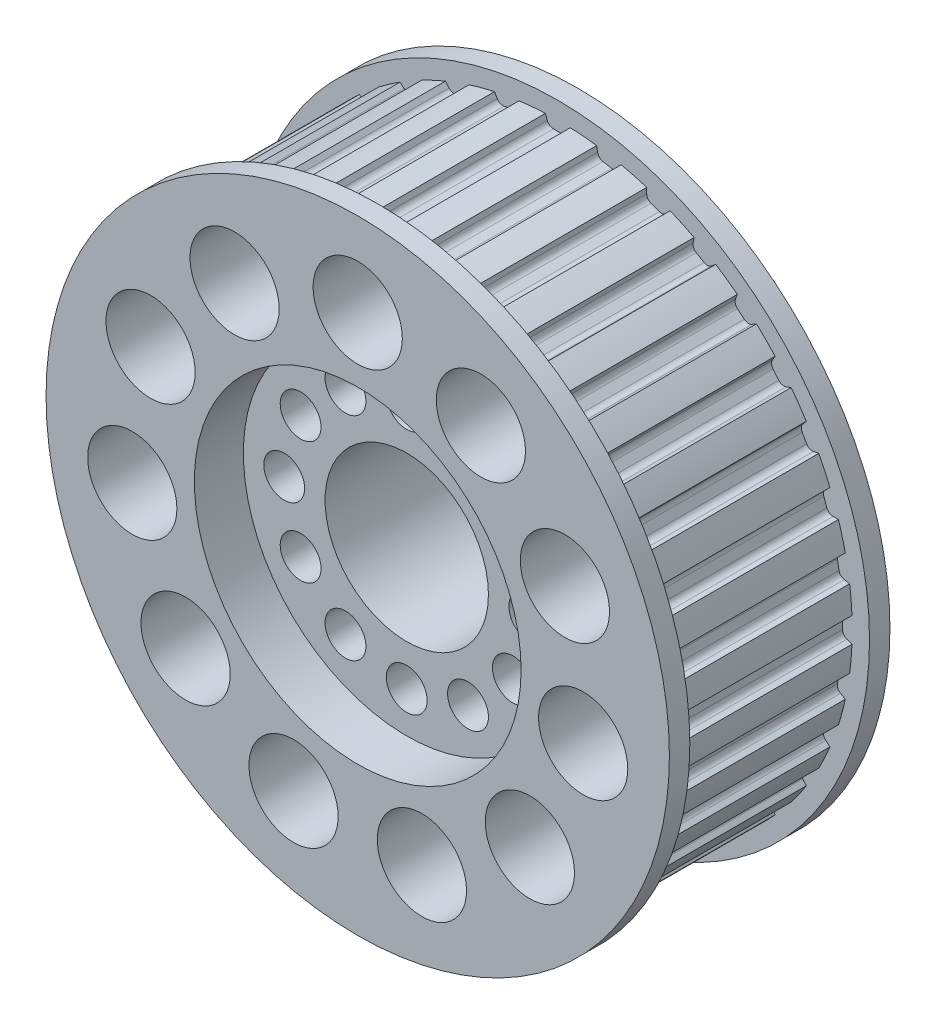
SolidWorks part; units mm, degrees
note: '?' marks a value the reader was unsure of.
extrude "Base-Extrude" add sketch "Sketch1" along normal mid plane 50
sketch "Sketch1" plane through (0, 0, 0) normal (0, 0, 1) x (1, 0, 0)
  circle A0 centre (0, 0) radius 72.0656
  dimension "D1" = 144.1313
material "Nylon 6/10"
ref_plane "Front" through (0, 0, 0) normal (0, 0, 1) x (1, 0, 0)
ref_plane "Top" through (0, 0, 0) normal (0, 1, 0) x (1, 0, 0)
ref_plane "Right" through (0, 0, 0) normal (1, 0, 0) x (0, 0, -1)
sketch "Sketch2" plane through (0, 0, 0) normal (0, 0, 1) x (1, 0, 0)
  line L0 (0, 0) -> (0, 56.1155) construction
  line L1 (-3.05, 72.0011) -> (-2.2129, 69.7011)
  line L2 (-2.2129, 69.7011) -> (2.2129, 69.7011)
  line L3 (2.2129, 69.7011) -> (3.05, 72.0011)
  circle A0 centre (0, 0) radius 72.0656 construction
  dimension "D1" = 6.1
  dimension "D2" = 3.05
  dimension "D3" = 2.3
  dimension "D4" = 40
  dimension "D5" = 20
extrude "Cut-Extrude1" cut sketch "Sketch2" against normal through all and the other way through all
fillet "Fillet1" radius 1.6 2 edges at (-2.2129, 69.7011, 0) (2.2129, 69.7011, 0)
ref_axis "PulleyAxis" through (0, 0, -29.7) along (0, 0, 1)?
pattern_circular "CirPattern1" count 36 every 10 about axis through (0, 0, 0) along (0, 0, 1) of "Fillet1", "Cut-Extrude1"
ref_plane "Plane1" through (228.6, 0, 0) normal (1, 0, 0) x (0, 0, -1)
ref_axis "AxisDistance" through (228.6, 0, 29.7) along (0, 0, -1)?
sketch "Sketch7" plane through (0, 0, 25) normal (0, 0, 1) x (1, 0, 0)
  circle A0 centre (0, 0) radius 40
  dimension "D1" = 80
extrude "Cut-Extrude4" cut sketch "Sketch7" against normal blind 10
sketch "Sketch12" plane through (0, 0, 25) normal (0, 0, 1) x (1, 0, 0)
  circle A0 centre (0, 0) radius 40
  circle A1 centre (0, 0) radius 75
  dimension "D2" = 150
  dimension "D1" = 80
extrude "Cut-Extrude7" cut sketch "Sketch12" against normal blind 3
sketch "Sketch13" plane through (0, 0, -25) normal (0, 0, -1) x (-1, 0, 0)
  circle A0 centre (0, 0) radius 40
  circle A1 centre (0, 0) radius 75
  dimension "D2" = 150
  dimension "D1" = 80
extrude "Cut-Extrude8" cut sketch "Sketch13" against normal blind 3
sketch "Sketch15" plane through (0, 0, 22) normal (0, 0, 1) x (1, 0, 0)
  line L0 (0, 69.7011) -> (0, 0) construction
  line L1 (-1.0925, 69.7011) -> (1.0925, 69.7011) construction
  circle A0 centre (0, 60) radius 1.5
  dimension "D1" = 3
  dimension "D2" = 60
extrude "Cut-Extrude10" cut sketch "Sketch15" against normal blind 60
pattern_circular "CirPattern2" count 12 over 360 about axis through (0, 0, 0) along (0, 0, 1) of "Cut-Extrude10"
sketch "Sketch16" plane through (0, 0, -25) normal (0, 0, -1) x (-1, 0, 0)
  line L0 (0, 0) -> (0, 40) construction
  circle A0 centre (0, 0) radius 40 construction
  circle A1 centre (0, 30) radius 5
  circle A2 centre (15, 25.9808) radius 5
  circle A3 centre (25.9808, 15) radius 5
  circle A4 centre (30, 0) radius 5
  circle A5 centre (25.9808, -15) radius 5
  circle A6 centre (15, -25.9808) radius 5
  circle A7 centre (0, -30) radius 5
  circle A8 centre (-15, -25.9808) radius 5
  circle A9 centre (-25.9808, -15) radius 5
  circle A10 centre (-30, 0) radius 5
  circle A11 centre (-25.9808, 15) radius 5
  circle A12 centre (-15, 25.9808) radius 5
  dimension "D1" = 10
  dimension "D2" = 30
extrude "Cut-Extrude11" cut sketch "Sketch16" against normal blind 50
sketch "Sketch17" plane through (0, 0, -25) normal (0, 0, -1) x (-1, 0, 0)
  circle A0 centre (0, 0) radius 13.5
  dimension "D1" = 27
extrude "Cut-Extrude12" cut sketch "Sketch17" against normal blind 50
sketch "Sketch19" plane through (0, 0, 22) normal (0, 0, 1) x (1, 0, 0)
  line L0 (0, 60) -> (30, 51.9615) construction
  line L1 (0, 0) -> (15, 55.9808) construction
  circle A0 centre (14.235, 53.1259) radius 10
  dimension "D1" = 55
  dimension "D2" = 20
extrude "Cut-Extrude14" cut sketch "Sketch19" against normal blind 60
pattern_circular "CirPattern3" count 12 over 360 about axis through (0, 0, 0) along (0, 0, 1) of "Cut-Extrude14"
sketch "Sketch20" plane through (0, 0, -25) normal (0, 0, -1) x (-1, 0, 0)
  circle A0 centre (0, 0) radius 40
  dimension "D1" = 80
extrude "Cut-Extrude15" cut sketch "Sketch20" against normal blind 8
sketch "Sketch24" plane through (0, 0, -17) normal (0, 0, -1) x (-1, 0, 0)
  circle A0 centre (0, 0) radius 16
  dimension "D1" = 32
extrude "Cut-Extrude18" cut sketch "Sketch24" against normal blind 10
sketch "Sketch25" plane through (0, 0, 15) normal (0, 0, 1) x (1, 0, 0)
  circle A0 centre (0, 0) radius 16
  dimension "D1" = 32
extrude "Cut-Extrude19" cut sketch "Sketch25" against normal blind 10
sketch "Sketch26" plane through (0, 0, 22) normal (0, 0, 1) x (1, 0, 0)
  line L108 (-13.1794, -68.4524) -> (-11.0275, -68.8319)
  line L109 (-9.7297, -70.1297) -> (-9.4992, -71.4368)
  line L110 (-3.05, -72.0011) -> (-2.596, -70.7538)
  line L111 (-1.0925, -69.7011) -> (1.0925, -69.7011)
  line L112 (2.596, -70.7538) -> (3.05, -72.0011)
  line L113 (9.4992, -71.4368) -> (9.7297, -70.1297)
  line L114 (11.0275, -68.8319) -> (13.1794, -68.4524)
  line L115 (14.8429, -69.2281) -> (15.5065, -70.3776)
  line L116 (21.7598, -68.702) -> (21.7598, -67.3748)
  line L117 (22.8125, -65.8712) -> (24.8658, -65.1239)
  line L118 (26.6387, -65.599) -> (27.4919, -66.6157)
  line L119 (33.3592, -63.8798) -> (33.1287, -62.5726)
  line L120 (33.9044, -60.9092) -> (35.7967, -59.8166)
  line L121 (37.6252, -59.9766) -> (38.6419, -60.8298)
  line L122 (43.945, -57.1165) -> (43.491, -55.8693)
  line L123 (43.9661, -54.0964) -> (45.6399, -52.6918)
  line L124 (47.4684, -52.5319) -> (48.6178, -53.1955)
  line L125 (53.1955, -48.6178) -> (52.5319, -47.4684)
  line L126 (52.6918, -45.6399) -> (54.0964, -43.9661)
  line L127 (55.8693, -43.491) -> (57.1165, -43.945)
  line L128 (60.8298, -38.6419) -> (59.9766, -37.6252)
  line L129 (59.8166, -35.7967) -> (60.9092, -33.9044)
  line L130 (62.5726, -33.1287) -> (63.8798, -33.3592)
  line L131 (66.6157, -27.4919) -> (65.599, -26.6387)
  line L132 (65.1239, -24.8658) -> (65.8712, -22.8125)
  line L133 (67.3748, -21.7598) -> (68.702, -21.7598)
  line L134 (70.3776, -15.5065) -> (69.2281, -14.8429)
  line L135 (68.4524, -13.1794) -> (68.8319, -11.0275)
  line L136 (70.1297, -9.7297) -> (71.4368, -9.4992)
  line L137 (72.0011, -3.05) -> (70.7538, -2.596)
  line L138 (69.7011, -1.0925) -> (69.7011, 1.0925)
  line L139 (70.7538, 2.596) -> (72.0011, 3.05)
  line L140 (71.4368, 9.4992) -> (70.1297, 9.7297)
  line L141 (68.8319, 11.0275) -> (68.4524, 13.1794)
  line L142 (69.2281, 14.8429) -> (70.3776, 15.5065)
  line L143 (68.702, 21.7598) -> (67.3748, 21.7598)
  line L144 (65.8712, 22.8125) -> (65.1239, 24.8658)
  line L145 (65.599, 26.6387) -> (66.6157, 27.4919)
  line L146 (63.8798, 33.3592) -> (62.5726, 33.1287)
  line L147 (60.9092, 33.9044) -> (59.8166, 35.7967)
  line L148 (59.9766, 37.6252) -> (60.8298, 38.6419)
  line L149 (57.1165, 43.945) -> (55.8693, 43.491)
  line L150 (54.0964, 43.9661) -> (52.6918, 45.6399)
  line L151 (52.5319, 47.4684) -> (53.1955, 48.6178)
  line L152 (48.6178, 53.1955) -> (47.4684, 52.5319)
  line L153 (45.6399, 52.6918) -> (43.9661, 54.0964)
  line L154 (43.491, 55.8693) -> (43.945, 57.1165)
  line L155 (38.6419, 60.8298) -> (37.6252, 59.9766)
  line L156 (35.7967, 59.8166) -> (33.9044, 60.9092)
  line L157 (33.1287, 62.5726) -> (33.3592, 63.8798)
  line L158 (27.4919, 66.6157) -> (26.6387, 65.599)
  line L159 (24.8658, 65.1239) -> (22.8125, 65.8712)
  line L160 (21.7598, 67.3748) -> (21.7598, 68.702)
  line L161 (15.5065, 70.3776) -> (14.8429, 69.2281)
  line L162 (13.1794, 68.4524) -> (11.0275, 68.8319)
  line L163 (9.7297, 70.1297) -> (9.4992, 71.4368)
  line L164 (3.05, 72.0011) -> (2.596, 70.7538)
  line L165 (1.0925, 69.7011) -> (-1.0925, 69.7011)
  line L166 (-2.596, 70.7538) -> (-3.05, 72.0011)
  line L167 (-9.4992, 71.4368) -> (-9.7297, 70.1297)
  line L168 (-11.0275, 68.8319) -> (-13.1794, 68.4524)
  line L169 (-14.8429, 69.2281) -> (-15.5065, 70.3776)
  line L170 (-21.7598, 68.702) -> (-21.7598, 67.3748)
  line L171 (-22.8125, 65.8712) -> (-24.8658, 65.1239)
  line L172 (-26.6387, 65.599) -> (-27.4919, 66.6157)
  line L173 (-33.3592, 63.8798) -> (-33.1287, 62.5726)
  line L174 (-33.9044, 60.9092) -> (-35.7967, 59.8166)
  line L175 (-37.6252, 59.9766) -> (-38.6419, 60.8298)
  line L176 (-43.945, 57.1165) -> (-43.491, 55.8693)
  line L177 (-43.9661, 54.0964) -> (-45.6399, 52.6918)
  line L178 (-47.4684, 52.5319) -> (-48.6178, 53.1955)
  line L179 (-53.1955, 48.6178) -> (-52.5319, 47.4684)
  line L180 (-52.6918, 45.6399) -> (-54.0964, 43.9661)
  line L181 (-55.8693, 43.491) -> (-57.1165, 43.945)
  line L182 (-60.8298, 38.6419) -> (-59.9766, 37.6252)
  line L183 (-59.8166, 35.7967) -> (-60.9092, 33.9044)
  line L184 (-62.5726, 33.1287) -> (-63.8798, 33.3592)
  line L185 (-66.6157, 27.4919) -> (-65.599, 26.6387)
  line L186 (-65.1239, 24.8658) -> (-65.8712, 22.8125)
  line L187 (-67.3748, 21.7598) -> (-68.702, 21.7598)
  line L188 (-70.3776, 15.5065) -> (-69.2281, 14.8429)
  line L189 (-68.4524, 13.1794) -> (-68.8319, 11.0275)
  line L190 (-70.1297, 9.7297) -> (-71.4368, 9.4992)
  line L191 (-72.0011, 3.05) -> (-70.7538, 2.596)
  line L192 (-69.7011, 1.0925) -> (-69.7011, -1.0925)
  line L193 (-70.7538, -2.596) -> (-72.0011, -3.05)
  line L194 (-71.4368, -9.4992) -> (-70.1297, -9.7297)
  line L195 (-68.8319, -11.0275) -> (-68.4524, -13.1794)
  line L196 (-69.2281, -14.8429) -> (-70.3776, -15.5065)
  line L197 (-68.702, -21.7598) -> (-67.3748, -21.7598)
  line L198 (-65.8712, -22.8125) -> (-65.1239, -24.8658)
  line L199 (-65.599, -26.6387) -> (-66.6157, -27.4919)
  line L200 (-63.8798, -33.3592) -> (-62.5726, -33.1287)
  line L201 (-60.9092, -33.9044) -> (-59.8166, -35.7967)
  line L202 (-59.9766, -37.6252) -> (-60.8298, -38.6419)
  line L203 (-57.1165, -43.945) -> (-55.8693, -43.491)
  line L204 (-54.0964, -43.9661) -> (-52.6918, -45.6399)
  line L205 (-52.5319, -47.4684) -> (-53.1955, -48.6178)
  line L206 (-48.6178, -53.1955) -> (-47.4684, -52.5319)
  line L207 (-45.6399, -52.6918) -> (-43.9661, -54.0964)
  line L208 (-43.491, -55.8693) -> (-43.945, -57.1165)
  line L209 (-38.6419, -60.8298) -> (-37.6252, -59.9766)
  line L210 (-35.7967, -59.8166) -> (-33.9044, -60.9092)
  line L211 (-33.1287, -62.5726) -> (-33.3592, -63.8798)
  line L212 (-27.4919, -66.6157) -> (-26.6387, -65.599)
  line L213 (-24.8658, -65.1239) -> (-22.8125, -65.8712)
  line L214 (-21.7598, -67.3748) -> (-21.7598, -68.702)
  line L215 (-15.5065, -70.3776) -> (-14.8429, -69.2281)
  line L216 (-13.1794, -68.4524) -> (-11.0275, -68.8319)
  line L217 (-9.7297, -70.1297) -> (-9.4992, -71.4368)
  line L218 (-3.05, -72.0011) -> (-2.596, -70.7538)
  line L219 (-1.0925, -69.7011) -> (1.0925, -69.7011)
  line L220 (2.596, -70.7538) -> (3.05, -72.0011)
  line L221 (9.4992, -71.4368) -> (9.7297, -70.1297)
  line L222 (11.0275, -68.8319) -> (13.1794, -68.4524)
  line L223 (14.8429, -69.2281) -> (15.5065, -70.3776)
  line L224 (21.7598, -68.702) -> (21.7598, -67.3748)
  line L225 (22.8125, -65.8712) -> (24.8658, -65.1239)
  line L226 (26.6387, -65.599) -> (27.4919, -66.6157)
  line L227 (33.3592, -63.8798) -> (33.1287, -62.5726)
  line L228 (33.9044, -60.9092) -> (35.7967, -59.8166)
  line L229 (37.6252, -59.9766) -> (38.6419, -60.8298)
  line L230 (43.945, -57.1165) -> (43.491, -55.8693)
  line L231 (43.9661, -54.0964) -> (45.6399, -52.6918)
  line L232 (47.4684, -52.5319) -> (48.6178, -53.1955)
  line L233 (53.1955, -48.6178) -> (52.5319, -47.4684)
  line L234 (52.6918, -45.6399) -> (54.0964, -43.9661)
  line L235 (55.8693, -43.491) -> (57.1165, -43.945)
  line L236 (60.8298, -38.6419) -> (59.9766, -37.6252)
  line L237 (59.8166, -35.7967) -> (60.9092, -33.9044)
  line L238 (62.5726, -33.1287) -> (63.8798, -33.3592)
  line L239 (66.6157, -27.4919) -> (65.599, -26.6387)
  line L240 (65.1239, -24.8658) -> (65.8712, -22.8125)
  line L241 (67.3748, -21.7598) -> (68.702, -21.7598)
  line L242 (70.3776, -15.5065) -> (69.2281, -14.8429)
  line L243 (68.4524, -13.1794) -> (68.8319, -11.0275)
  line L244 (70.1297, -9.7297) -> (71.4368, -9.4992)
  line L245 (72.0011, -3.05) -> (70.7538, -2.596)
  line L246 (69.7011, -1.0925) -> (69.7011, 1.0925)
  line L247 (70.7538, 2.596) -> (72.0011, 3.05)
  line L248 (71.4368, 9.4992) -> (70.1297, 9.7297)
  line L249 (68.8319, 11.0275) -> (68.4524, 13.1794)
  line L250 (69.2281, 14.8429) -> (70.3776, 15.5065)
  line L251 (68.702, 21.7598) -> (67.3748, 21.7598)
  line L252 (65.8712, 22.8125) -> (65.1239, 24.8658)
  line L253 (65.599, 26.6387) -> (66.6157, 27.4919)
  line L254 (63.8798, 33.3592) -> (62.5726, 33.1287)
  line L255 (60.9092, 33.9044) -> (59.8166, 35.7967)
  line L256 (59.9766, 37.6252) -> (60.8298, 38.6419)
  line L257 (57.1165, 43.945) -> (55.8693, 43.491)
  line L258 (54.0964, 43.9661) -> (52.6918, 45.6399)
  line L259 (52.5319, 47.4684) -> (53.1955, 48.6178)
  line L260 (48.6178, 53.1955) -> (47.4684, 52.5319)
  line L261 (45.6399, 52.6918) -> (43.9661, 54.0964)
  line L262 (43.491, 55.8693) -> (43.945, 57.1165)
  line L263 (38.6419, 60.8298) -> (37.6252, 59.9766)
  line L264 (35.7967, 59.8166) -> (33.9044, 60.9092)
  line L265 (33.1287, 62.5726) -> (33.3592, 63.8798)
  line L266 (27.4919, 66.6157) -> (26.6387, 65.599)
  line L267 (24.8658, 65.1239) -> (22.8125, 65.8712)
  line L268 (21.7598, 67.3748) -> (21.7598, 68.702)
  line L269 (15.5065, 70.3776) -> (14.8429, 69.2281)
  line L270 (13.1794, 68.4524) -> (11.0275, 68.8319)
  line L271 (9.7297, 70.1297) -> (9.4992, 71.4368)
  line L272 (3.05, 72.0011) -> (2.596, 70.7538)
  line L273 (1.0925, 69.7011) -> (-1.0925, 69.7011)
  line L274 (-2.596, 70.7538) -> (-3.05, 72.0011)
  line L275 (-9.4992, 71.4368) -> (-9.7297, 70.1297)
  line L276 (-11.0275, 68.8319) -> (-13.1794, 68.4524)
  line L277 (-14.8429, 69.2281) -> (-15.5065, 70.3776)
  line L278 (-21.7598, 68.702) -> (-21.7598, 67.3748)
  line L279 (-22.8125, 65.8712) -> (-24.8658, 65.1239)
  line L280 (-26.6387, 65.599) -> (-27.4919, 66.6157)
  line L281 (-33.3592, 63.8798) -> (-33.1287, 62.5726)
  line L282 (-33.9044, 60.9092) -> (-35.7967, 59.8166)
  line L283 (-37.6252, 59.9766) -> (-38.6419, 60.8298)
  line L284 (-43.945, 57.1165) -> (-43.491, 55.8693)
  line L285 (-43.9661, 54.0964) -> (-45.6399, 52.6918)
  line L286 (-47.4684, 52.5319) -> (-48.6178, 53.1955)
  line L287 (-53.1955, 48.6178) -> (-52.5319, 47.4684)
  line L288 (-52.6918, 45.6399) -> (-54.0964, 43.9661)
  line L289 (-55.8693, 43.491) -> (-57.1165, 43.945)
  line L290 (-60.8298, 38.6419) -> (-59.9766, 37.6252)
  line L291 (-59.8166, 35.7967) -> (-60.9092, 33.9044)
  line L292 (-62.5726, 33.1287) -> (-63.8798, 33.3592)
  line L293 (-66.6157, 27.4919) -> (-65.599, 26.6387)
  line L294 (-65.1239, 24.8658) -> (-65.8712, 22.8125)
  line L295 (-67.3748, 21.7598) -> (-68.702, 21.7598)
  line L296 (-70.3776, 15.5065) -> (-69.2281, 14.8429)
  line L297 (-68.4524, 13.1794) -> (-68.8319, 11.0275)
  line L298 (-70.1297, 9.7297) -> (-71.4368, 9.4992)
  line L299 (-72.0011, 3.05) -> (-70.7538, 2.596)
  line L300 (-69.7011, 1.0925) -> (-69.7011, -1.0925)
  line L301 (-70.7538, -2.596) -> (-72.0011, -3.05)
  line L302 (-71.4368, -9.4992) -> (-70.1297, -9.7297)
  line L303 (-68.8319, -11.0275) -> (-68.4524, -13.1794)
  line L304 (-69.2281, -14.8429) -> (-70.3776, -15.5065)
  line L305 (-68.702, -21.7598) -> (-67.3748, -21.7598)
  line L306 (-65.8712, -22.8125) -> (-65.1239, -24.8658)
  line L307 (-65.599, -26.6387) -> (-66.6157, -27.4919)
  line L308 (-63.8798, -33.3592) -> (-62.5726, -33.1287)
  line L309 (-60.9092, -33.9044) -> (-59.8166, -35.7967)
  line L310 (-59.9766, -37.6252) -> (-60.8298, -38.6419)
  line L311 (-57.1165, -43.945) -> (-55.8693, -43.491)
  line L312 (-54.0964, -43.9661) -> (-52.6918, -45.6399)
  line L313 (-52.5319, -47.4684) -> (-53.1955, -48.6178)
  line L314 (-48.6178, -53.1955) -> (-47.4684, -52.5319)
  line L315 (-45.6399, -52.6918) -> (-43.9661, -54.0964)
  line L316 (-43.491, -55.8693) -> (-43.945, -57.1165)
  line L317 (-38.6419, -60.8298) -> (-37.6252, -59.9766)
  line L318 (-35.7967, -59.8166) -> (-33.9044, -60.9092)
  line L319 (-33.1287, -62.5726) -> (-33.3592, -63.8798)
  line L320 (-27.4919, -66.6157) -> (-26.6387, -65.599)
  line L321 (-24.8658, -65.1239) -> (-22.8125, -65.8712)
  line L322 (-21.7598, -67.3748) -> (-21.7598, -68.702)
  line L323 (-15.5065, -70.3776) -> (-14.8429, -69.2281)
  circle A0 centre (0, 0) radius 40 construction
  circle A1 centre (0, 0) radius 40
  arc A108 (-13.1794, -68.4524) -> (-14.8429, -69.2281) centre (-13.4572, -70.0281) ccw
  arc A109 (-9.7297, -70.1297) -> (-11.0275, -68.8319) centre (-11.3054, -70.4076) ccw
  arc A110 (-9.4992, -71.4368) -> (-3.05, -72.0011) centre (0, 0) ccw
  arc A111 (-1.0925, -69.7011) -> (-2.596, -70.7538) centre (-1.0925, -71.3011) ccw
  arc A112 (2.596, -70.7538) -> (1.0925, -69.7011) centre (1.0925, -71.3011) ccw
  arc A113 (3.05, -72.0011) -> (9.4992, -71.4368) centre (0, 0) ccw
  arc A114 (11.0275, -68.8319) -> (9.7297, -70.1297) centre (11.3054, -70.4076) ccw
  arc A115 (14.8429, -69.2281) -> (13.1794, -68.4524) centre (13.4572, -70.0281) ccw
  arc A116 (15.5065, -70.3776) -> (21.7598, -68.702) centre (0, 0) ccw
  arc A117 (22.8125, -65.8712) -> (21.7598, -67.3748) centre (23.3598, -67.3748) ccw
  arc A118 (26.6387, -65.599) -> (24.8658, -65.1239) centre (25.4131, -66.6274) ccw
  arc A119 (27.4919, -66.6157) -> (33.3592, -63.8798) centre (0, 0) ccw
  arc A120 (33.9044, -60.9092) -> (33.1287, -62.5726) centre (34.7044, -62.2948) ccw
  arc A121 (37.6252, -59.9766) -> (35.7967, -59.8166) centre (36.5967, -61.2023) ccw
  arc A122 (38.6419, -60.8298) -> (43.945, -57.1165) centre (0, 0) ccw
  arc A123 (43.9661, -54.0964) -> (43.491, -55.8693) centre (44.9945, -55.3221) ccw
  arc A124 (47.4684, -52.5319) -> (45.6399, -52.6918) centre (46.6684, -53.9175) ccw
  arc A125 (48.6178, -53.1955) -> (53.1955, -48.6178) centre (0, 0) ccw
  arc A126 (52.6918, -45.6399) -> (52.5319, -47.4684) centre (53.9175, -46.6684) ccw
  arc A127 (55.8693, -43.491) -> (54.0964, -43.9661) centre (55.3221, -44.9945) ccw
  arc A128 (57.1165, -43.945) -> (60.8298, -38.6419) centre (0, 0) ccw
  arc A129 (59.8166, -35.7967) -> (59.9766, -37.6252) centre (61.2023, -36.5967) ccw
  arc A130 (62.5726, -33.1287) -> (60.9092, -33.9044) centre (62.2948, -34.7044) ccw
  arc A131 (63.8798, -33.3592) -> (66.6157, -27.4919) centre (0, 0) ccw
  arc A132 (65.1239, -24.8658) -> (65.599, -26.6387) centre (66.6274, -25.4131) ccw
  arc A133 (67.3748, -21.7598) -> (65.8712, -22.8125) centre (67.3748, -23.3598) ccw
  arc A134 (68.702, -21.7598) -> (70.3776, -15.5065) centre (0, 0) ccw
  arc A135 (68.4524, -13.1794) -> (69.2281, -14.8429) centre (70.0281, -13.4572) ccw
  arc A136 (70.1297, -9.7297) -> (68.8319, -11.0275) centre (70.4076, -11.3054) ccw
  arc A137 (71.4368, -9.4992) -> (72.0011, -3.05) centre (0, 0) ccw
  arc A138 (69.7011, -1.0925) -> (70.7538, -2.596) centre (71.3011, -1.0925) ccw
  arc A139 (70.7538, 2.596) -> (69.7011, 1.0925) centre (71.3011, 1.0925) ccw
  arc A140 (72.0011, 3.05) -> (71.4368, 9.4992) centre (0, 0) ccw
  arc A141 (68.8319, 11.0275) -> (70.1297, 9.7297) centre (70.4076, 11.3054) ccw
  arc A142 (69.2281, 14.8429) -> (68.4524, 13.1794) centre (70.0281, 13.4572) ccw
  arc A143 (70.3776, 15.5065) -> (68.702, 21.7598) centre (0, 0) ccw
  arc A144 (65.8712, 22.8125) -> (67.3748, 21.7598) centre (67.3748, 23.3598) ccw
  arc A145 (65.599, 26.6387) -> (65.1239, 24.8658) centre (66.6274, 25.4131) ccw
  arc A146 (66.6157, 27.4919) -> (63.8798, 33.3592) centre (0, 0) ccw
  arc A147 (60.9092, 33.9044) -> (62.5726, 33.1287) centre (62.2948, 34.7044) ccw
  arc A148 (59.9766, 37.6252) -> (59.8166, 35.7967) centre (61.2023, 36.5967) ccw
  arc A149 (60.8298, 38.6419) -> (57.1165, 43.945) centre (0, 0) ccw
  arc A150 (54.0964, 43.9661) -> (55.8693, 43.491) centre (55.3221, 44.9945) ccw
  arc A151 (52.5319, 47.4684) -> (52.6918, 45.6399) centre (53.9175, 46.6684) ccw
  arc A152 (53.1955, 48.6178) -> (48.6178, 53.1955) centre (0, 0) ccw
  arc A153 (45.6399, 52.6918) -> (47.4684, 52.5319) centre (46.6684, 53.9175) ccw
  arc A154 (43.491, 55.8693) -> (43.9661, 54.0964) centre (44.9945, 55.3221) ccw
  arc A155 (43.945, 57.1165) -> (38.6419, 60.8298) centre (0, 0) ccw
  arc A156 (35.7967, 59.8166) -> (37.6252, 59.9766) centre (36.5967, 61.2023) ccw
  arc A157 (33.1287, 62.5726) -> (33.9044, 60.9092) centre (34.7044, 62.2948) ccw
  arc A158 (33.3592, 63.8798) -> (27.4919, 66.6157) centre (0, 0) ccw
  arc A159 (24.8658, 65.1239) -> (26.6387, 65.599) centre (25.4131, 66.6274) ccw
  arc A160 (21.7598, 67.3748) -> (22.8125, 65.8712) centre (23.3598, 67.3748) ccw
  arc A161 (21.7598, 68.702) -> (15.5065, 70.3776) centre (0, 0) ccw
  arc A162 (13.1794, 68.4524) -> (14.8429, 69.2281) centre (13.4572, 70.0281) ccw
  arc A163 (9.7297, 70.1297) -> (11.0275, 68.8319) centre (11.3054, 70.4076) ccw
  arc A164 (9.4992, 71.4368) -> (3.05, 72.0011) centre (0, 0) ccw
  arc A165 (1.0925, 69.7011) -> (2.596, 70.7538) centre (1.0925, 71.3011) ccw
  arc A166 (-2.596, 70.7538) -> (-1.0925, 69.7011) centre (-1.0925, 71.3011) ccw
  arc A167 (-3.05, 72.0011) -> (-9.4992, 71.4368) centre (0, 0) ccw
  arc A168 (-11.0275, 68.8319) -> (-9.7297, 70.1297) centre (-11.3054, 70.4076) ccw
  arc A169 (-14.8429, 69.2281) -> (-13.1794, 68.4524) centre (-13.4572, 70.0281) ccw
  arc A170 (-15.5065, 70.3776) -> (-21.7598, 68.702) centre (0, 0) ccw
  arc A171 (-22.8125, 65.8712) -> (-21.7598, 67.3748) centre (-23.3598, 67.3748) ccw
  arc A172 (-26.6387, 65.599) -> (-24.8658, 65.1239) centre (-25.4131, 66.6274) ccw
  arc A173 (-27.4919, 66.6157) -> (-33.3592, 63.8798) centre (0, 0) ccw
  arc A174 (-33.9044, 60.9092) -> (-33.1287, 62.5726) centre (-34.7044, 62.2948) ccw
  arc A175 (-37.6252, 59.9766) -> (-35.7967, 59.8166) centre (-36.5967, 61.2023) ccw
  arc A176 (-38.6419, 60.8298) -> (-43.945, 57.1165) centre (0, 0) ccw
  arc A177 (-43.9661, 54.0964) -> (-43.491, 55.8693) centre (-44.9945, 55.3221) ccw
  arc A178 (-47.4684, 52.5319) -> (-45.6399, 52.6918) centre (-46.6684, 53.9175) ccw
  arc A179 (-48.6178, 53.1955) -> (-53.1955, 48.6178) centre (0, 0) ccw
  arc A180 (-52.6918, 45.6399) -> (-52.5319, 47.4684) centre (-53.9175, 46.6684) ccw
  arc A181 (-55.8693, 43.491) -> (-54.0964, 43.9661) centre (-55.3221, 44.9945) ccw
  arc A182 (-57.1165, 43.945) -> (-60.8298, 38.6419) centre (0, 0) ccw
  arc A183 (-59.8166, 35.7967) -> (-59.9766, 37.6252) centre (-61.2023, 36.5967) ccw
  arc A184 (-62.5726, 33.1287) -> (-60.9092, 33.9044) centre (-62.2948, 34.7044) ccw
  arc A185 (-63.8798, 33.3592) -> (-66.6157, 27.4919) centre (0, 0) ccw
  arc A186 (-65.1239, 24.8658) -> (-65.599, 26.6387) centre (-66.6274, 25.4131) ccw
  arc A187 (-67.3748, 21.7598) -> (-65.8712, 22.8125) centre (-67.3748, 23.3598) ccw
  arc A188 (-68.702, 21.7598) -> (-70.3776, 15.5065) centre (0, 0) ccw
  arc A189 (-68.4524, 13.1794) -> (-69.2281, 14.8429) centre (-70.0281, 13.4572) ccw
  arc A190 (-70.1297, 9.7297) -> (-68.8319, 11.0275) centre (-70.4076, 11.3054) ccw
  arc A191 (-71.4368, 9.4992) -> (-72.0011, 3.05) centre (0, 0) ccw
  arc A192 (-69.7011, 1.0925) -> (-70.7538, 2.596) centre (-71.3011, 1.0925) ccw
  arc A193 (-70.7538, -2.596) -> (-69.7011, -1.0925) centre (-71.3011, -1.0925) ccw
  arc A194 (-72.0011, -3.05) -> (-71.4368, -9.4992) centre (0, 0) ccw
  arc A195 (-68.8319, -11.0275) -> (-70.1297, -9.7297) centre (-70.4076, -11.3054) ccw
  arc A196 (-69.2281, -14.8429) -> (-68.4524, -13.1794) centre (-70.0281, -13.4572) ccw
  arc A197 (-70.3776, -15.5065) -> (-68.702, -21.7598) centre (0, 0) ccw
  arc A198 (-65.8712, -22.8125) -> (-67.3748, -21.7598) centre (-67.3748, -23.3598) ccw
  arc A199 (-65.599, -26.6387) -> (-65.1239, -24.8658) centre (-66.6274, -25.4131) ccw
  arc A200 (-66.6157, -27.4919) -> (-63.8798, -33.3592) centre (0, 0) ccw
  arc A201 (-60.9092, -33.9044) -> (-62.5726, -33.1287) centre (-62.2948, -34.7044) ccw
  arc A202 (-59.9766, -37.6252) -> (-59.8166, -35.7967) centre (-61.2023, -36.5967) ccw
  arc A203 (-60.8298, -38.6419) -> (-57.1165, -43.945) centre (0, 0) ccw
  arc A204 (-54.0964, -43.9661) -> (-55.8693, -43.491) centre (-55.3221, -44.9945) ccw
  arc A205 (-52.5319, -47.4684) -> (-52.6918, -45.6399) centre (-53.9175, -46.6684) ccw
  arc A206 (-53.1955, -48.6178) -> (-48.6178, -53.1955) centre (0, 0) ccw
  arc A207 (-45.6399, -52.6918) -> (-47.4684, -52.5319) centre (-46.6684, -53.9175) ccw
  arc A208 (-43.491, -55.8693) -> (-43.9661, -54.0964) centre (-44.9945, -55.3221) ccw
  arc A209 (-43.945, -57.1165) -> (-38.6419, -60.8298) centre (0, 0) ccw
  arc A210 (-35.7967, -59.8166) -> (-37.6252, -59.9766) centre (-36.5967, -61.2023) ccw
  arc A211 (-33.1287, -62.5726) -> (-33.9044, -60.9092) centre (-34.7044, -62.2948) ccw
  arc A212 (-33.3592, -63.8798) -> (-27.4919, -66.6157) centre (0, 0) ccw
  arc A213 (-24.8658, -65.1239) -> (-26.6387, -65.599) centre (-25.4131, -66.6274) ccw
  arc A214 (-21.7598, -67.3748) -> (-22.8125, -65.8712) centre (-23.3598, -67.3748) ccw
  arc A215 (-21.7598, -68.702) -> (-15.5065, -70.3776) centre (0, 0) ccw
  arc A216 (-13.1794, -68.4524) -> (-14.8429, -69.2281) centre (-13.4572, -70.0281) ccw
  arc A217 (-9.7297, -70.1297) -> (-11.0275, -68.8319) centre (-11.3054, -70.4076) ccw
  arc A218 (-9.4992, -71.4368) -> (-3.05, -72.0011) centre (0, 0) ccw
  arc A219 (-1.0925, -69.7011) -> (-2.596, -70.7538) centre (-1.0925, -71.3011) ccw
  arc A220 (2.596, -70.7538) -> (1.0925, -69.7011) centre (1.0925, -71.3011) ccw
  arc A221 (3.05, -72.0011) -> (9.4992, -71.4368) centre (0, 0) ccw
  arc A222 (11.0275, -68.8319) -> (9.7297, -70.1297) centre (11.3054, -70.4076) ccw
  arc A223 (14.8429, -69.2281) -> (13.1794, -68.4524) centre (13.4572, -70.0281) ccw
  arc A224 (15.5065, -70.3776) -> (21.7598, -68.702) centre (0, 0) ccw
  arc A225 (22.8125, -65.8712) -> (21.7598, -67.3748) centre (23.3598, -67.3748) ccw
  arc A226 (26.6387, -65.599) -> (24.8658, -65.1239) centre (25.4131, -66.6274) ccw
  arc A227 (27.4919, -66.6157) -> (33.3592, -63.8798) centre (0, 0) ccw
  arc A228 (33.9044, -60.9092) -> (33.1287, -62.5726) centre (34.7044, -62.2948) ccw
  arc A229 (37.6252, -59.9766) -> (35.7967, -59.8166) centre (36.5967, -61.2023) ccw
  arc A230 (38.6419, -60.8298) -> (43.945, -57.1165) centre (0, 0) ccw
  arc A231 (43.9661, -54.0964) -> (43.491, -55.8693) centre (44.9945, -55.3221) ccw
  arc A232 (47.4684, -52.5319) -> (45.6399, -52.6918) centre (46.6684, -53.9175) ccw
  arc A233 (48.6178, -53.1955) -> (53.1955, -48.6178) centre (0, 0) ccw
  arc A234 (52.6918, -45.6399) -> (52.5319, -47.4684) centre (53.9175, -46.6684) ccw
  arc A235 (55.8693, -43.491) -> (54.0964, -43.9661) centre (55.3221, -44.9945) ccw
  arc A236 (57.1165, -43.945) -> (60.8298, -38.6419) centre (0, 0) ccw
  arc A237 (59.8166, -35.7967) -> (59.9766, -37.6252) centre (61.2023, -36.5967) ccw
  arc A238 (62.5726, -33.1287) -> (60.9092, -33.9044) centre (62.2948, -34.7044) ccw
  arc A239 (63.8798, -33.3592) -> (66.6157, -27.4919) centre (0, 0) ccw
  arc A240 (65.1239, -24.8658) -> (65.599, -26.6387) centre (66.6274, -25.4131) ccw
  arc A241 (67.3748, -21.7598) -> (65.8712, -22.8125) centre (67.3748, -23.3598) ccw
  arc A242 (68.702, -21.7598) -> (70.3776, -15.5065) centre (0, 0) ccw
  arc A243 (68.4524, -13.1794) -> (69.2281, -14.8429) centre (70.0281, -13.4572) ccw
  arc A244 (70.1297, -9.7297) -> (68.8319, -11.0275) centre (70.4076, -11.3054) ccw
  arc A245 (71.4368, -9.4992) -> (72.0011, -3.05) centre (0, 0) ccw
  arc A246 (69.7011, -1.0925) -> (70.7538, -2.596) centre (71.3011, -1.0925) ccw
  arc A247 (70.7538, 2.596) -> (69.7011, 1.0925) centre (71.3011, 1.0925) ccw
  arc A248 (72.0011, 3.05) -> (71.4368, 9.4992) centre (0, 0) ccw
  arc A249 (68.8319, 11.0275) -> (70.1297, 9.7297) centre (70.4076, 11.3054) ccw
  arc A250 (69.2281, 14.8429) -> (68.4524, 13.1794) centre (70.0281, 13.4572) ccw
  arc A251 (70.3776, 15.5065) -> (68.702, 21.7598) centre (0, 0) ccw
  arc A252 (65.8712, 22.8125) -> (67.3748, 21.7598) centre (67.3748, 23.3598) ccw
  arc A253 (65.599, 26.6387) -> (65.1239, 24.8658) centre (66.6274, 25.4131) ccw
  arc A254 (66.6157, 27.4919) -> (63.8798, 33.3592) centre (0, 0) ccw
  arc A255 (60.9092, 33.9044) -> (62.5726, 33.1287) centre (62.2948, 34.7044) ccw
  arc A256 (59.9766, 37.6252) -> (59.8166, 35.7967) centre (61.2023, 36.5967) ccw
  arc A257 (60.8298, 38.6419) -> (57.1165, 43.945) centre (0, 0) ccw
  arc A258 (54.0964, 43.9661) -> (55.8693, 43.491) centre (55.3221, 44.9945) ccw
  arc A259 (52.5319, 47.4684) -> (52.6918, 45.6399) centre (53.9175, 46.6684) ccw
  arc A260 (53.1955, 48.6178) -> (48.6178, 53.1955) centre (0, 0) ccw
  arc A261 (45.6399, 52.6918) -> (47.4684, 52.5319) centre (46.6684, 53.9175) ccw
  arc A262 (43.491, 55.8693) -> (43.9661, 54.0964) centre (44.9945, 55.3221) ccw
  arc A263 (43.945, 57.1165) -> (38.6419, 60.8298) centre (0, 0) ccw
  arc A264 (35.7967, 59.8166) -> (37.6252, 59.9766) centre (36.5967, 61.2023) ccw
  arc A265 (33.1287, 62.5726) -> (33.9044, 60.9092) centre (34.7044, 62.2948) ccw
  arc A266 (33.3592, 63.8798) -> (27.4919, 66.6157) centre (0, 0) ccw
  arc A267 (24.8658, 65.1239) -> (26.6387, 65.599) centre (25.4131, 66.6274) ccw
  arc A268 (21.7598, 67.3748) -> (22.8125, 65.8712) centre (23.3598, 67.3748) ccw
  arc A269 (21.7598, 68.702) -> (15.5065, 70.3776) centre (0, 0) ccw
  arc A270 (13.1794, 68.4524) -> (14.8429, 69.2281) centre (13.4572, 70.0281) ccw
  arc A271 (9.7297, 70.1297) -> (11.0275, 68.8319) centre (11.3054, 70.4076) ccw
  arc A272 (9.4992, 71.4368) -> (3.05, 72.0011) centre (0, 0) ccw
  arc A273 (1.0925, 69.7011) -> (2.596, 70.7538) centre (1.0925, 71.3011) ccw
  arc A274 (-2.596, 70.7538) -> (-1.0925, 69.7011) centre (-1.0925, 71.3011) ccw
  arc A275 (-3.05, 72.0011) -> (-9.4992, 71.4368) centre (0, 0) ccw
  arc A276 (-11.0275, 68.8319) -> (-9.7297, 70.1297) centre (-11.3054, 70.4076) ccw
  arc A277 (-14.8429, 69.2281) -> (-13.1794, 68.4524) centre (-13.4572, 70.0281) ccw
  arc A278 (-15.5065, 70.3776) -> (-21.7598, 68.702) centre (0, 0) ccw
  arc A279 (-22.8125, 65.8712) -> (-21.7598, 67.3748) centre (-23.3598, 67.3748) ccw
  arc A280 (-26.6387, 65.599) -> (-24.8658, 65.1239) centre (-25.4131, 66.6274) ccw
  arc A281 (-27.4919, 66.6157) -> (-33.3592, 63.8798) centre (0, 0) ccw
  arc A282 (-33.9044, 60.9092) -> (-33.1287, 62.5726) centre (-34.7044, 62.2948) ccw
  arc A283 (-37.6252, 59.9766) -> (-35.7967, 59.8166) centre (-36.5967, 61.2023) ccw
  arc A284 (-38.6419, 60.8298) -> (-43.945, 57.1165) centre (0, 0) ccw
  arc A285 (-43.9661, 54.0964) -> (-43.491, 55.8693) centre (-44.9945, 55.3221) ccw
  arc A286 (-47.4684, 52.5319) -> (-45.6399, 52.6918) centre (-46.6684, 53.9175) ccw
  arc A287 (-48.6178, 53.1955) -> (-53.1955, 48.6178) centre (0, 0) ccw
  arc A288 (-52.6918, 45.6399) -> (-52.5319, 47.4684) centre (-53.9175, 46.6684) ccw
  arc A289 (-55.8693, 43.491) -> (-54.0964, 43.9661) centre (-55.3221, 44.9945) ccw
  arc A290 (-57.1165, 43.945) -> (-60.8298, 38.6419) centre (0, 0) ccw
  arc A291 (-59.8166, 35.7967) -> (-59.9766, 37.6252) centre (-61.2023, 36.5967) ccw
  arc A292 (-62.5726, 33.1287) -> (-60.9092, 33.9044) centre (-62.2948, 34.7044) ccw
  arc A293 (-63.8798, 33.3592) -> (-66.6157, 27.4919) centre (0, 0) ccw
  arc A294 (-65.1239, 24.8658) -> (-65.599, 26.6387) centre (-66.6274, 25.4131) ccw
  arc A295 (-67.3748, 21.7598) -> (-65.8712, 22.8125) centre (-67.3748, 23.3598) ccw
  arc A296 (-68.702, 21.7598) -> (-70.3776, 15.5065) centre (0, 0) ccw
  arc A297 (-68.4524, 13.1794) -> (-69.2281, 14.8429) centre (-70.0281, 13.4572) ccw
  arc A298 (-70.1297, 9.7297) -> (-68.8319, 11.0275) centre (-70.4076, 11.3054) ccw
  arc A299 (-71.4368, 9.4992) -> (-72.0011, 3.05) centre (0, 0) ccw
  arc A300 (-69.7011, 1.0925) -> (-70.7538, 2.596) centre (-71.3011, 1.0925) ccw
  arc A301 (-70.7538, -2.596) -> (-69.7011, -1.0925) centre (-71.3011, -1.0925) ccw
  arc A302 (-72.0011, -3.05) -> (-71.4368, -9.4992) centre (0, 0) ccw
  arc A303 (-68.8319, -11.0275) -> (-70.1297, -9.7297) centre (-70.4076, -11.3054) ccw
  arc A304 (-69.2281, -14.8429) -> (-68.4524, -13.1794) centre (-70.0281, -13.4572) ccw
  arc A305 (-70.3776, -15.5065) -> (-68.702, -21.7598) centre (0, 0) ccw
  arc A306 (-65.8712, -22.8125) -> (-67.3748, -21.7598) centre (-67.3748, -23.3598) ccw
  arc A307 (-65.599, -26.6387) -> (-65.1239, -24.8658) centre (-66.6274, -25.4131) ccw
  arc A308 (-66.6157, -27.4919) -> (-63.8798, -33.3592) centre (0, 0) ccw
  arc A309 (-60.9092, -33.9044) -> (-62.5726, -33.1287) centre (-62.2948, -34.7044) ccw
  arc A310 (-59.9766, -37.6252) -> (-59.8166, -35.7967) centre (-61.2023, -36.5967) ccw
  arc A311 (-60.8298, -38.6419) -> (-57.1165, -43.945) centre (0, 0) ccw
  arc A312 (-54.0964, -43.9661) -> (-55.8693, -43.491) centre (-55.3221, -44.9945) ccw
  arc A313 (-52.5319, -47.4684) -> (-52.6918, -45.6399) centre (-53.9175, -46.6684) ccw
  arc A314 (-53.1955, -48.6178) -> (-48.6178, -53.1955) centre (0, 0) ccw
  arc A315 (-45.6399, -52.6918) -> (-47.4684, -52.5319) centre (-46.6684, -53.9175) ccw
  arc A316 (-43.491, -55.8693) -> (-43.9661, -54.0964) centre (-44.9945, -55.3221) ccw
  arc A317 (-43.945, -57.1165) -> (-38.6419, -60.8298) centre (0, 0) ccw
  arc A318 (-35.7967, -59.8166) -> (-37.6252, -59.9766) centre (-36.5967, -61.2023) ccw
  arc A319 (-33.1287, -62.5726) -> (-33.9044, -60.9092) centre (-34.7044, -62.2948) ccw
  arc A320 (-33.3592, -63.8798) -> (-27.4919, -66.6157) centre (0, 0) ccw
  arc A321 (-24.8658, -65.1239) -> (-26.6387, -65.599) centre (-25.4131, -66.6274) ccw
  arc A322 (-21.7598, -67.3748) -> (-22.8125, -65.8712) centre (-23.3598, -67.3748) ccw
  arc A323 (-21.7598, -68.702) -> (-15.5065, -70.3776) centre (0, 0) ccw
  dimension "D1" = 0
extrude "Boss-Extrude1" add sketch "Sketch26" against normal through all
sketch "Sketch27" plane through (0, 0, 22) normal (0, 0, 1) x (1, 0, 0)
  arc A0 (-54.2677, 12.835) -> (-55.6855, 2.9739) centre (0, 0) ccw
  circle A1 centre (0, 55.7649) radius 10.921
  circle A2 centre (30.1488, 46.9124) radius 10.921
  circle A3 centre (50.7255, 23.1656) radius 10.921
  circle A4 centre (55.1973, -7.9362) radius 10.921
  circle A5 centre (42.1443, -36.5182) radius 10.921
  circle A6 centre (15.7108, -53.506) radius 10.921
  circle A7 centre (-15.7108, -53.506) radius 10.921
  circle A8 centre (-42.1443, -36.5182) radius 10.921
  circle A9 centre (-55.1973, -7.9362) radius 10.921
  circle A10 centre (-50.7255, 23.1656) radius 10.921
  circle A11 centre (-30.1488, 46.9124) radius 10.921
  arc A12 (-38.7138, 40.1368) -> (-45.2378, 32.6077) centre (0, 0) ccw
  arc A13 (-10.8685, 54.6955) -> (-20.4275, 51.8887) centre (0, 0) ccw
  arc A14 (20.4275, 51.8887) -> (10.8685, 54.6955) centre (0, 0) ccw
  arc A15 (45.2378, 32.6077) -> (38.7138, 40.1368) centre (0, 0) ccw
  arc A16 (55.6855, 2.9739) -> (54.2677, 12.835) centre (0, 0) ccw
  arc A17 (48.4535, -27.6041) -> (52.592, -18.5419) centre (0, 0) ccw
  arc A18 (25.8378, -49.4179) -> (34.2187, -44.0318) centre (0, 0) ccw
  arc A19 (-4.9813, -55.542) -> (4.9813, -55.542) centre (0, 0) ccw
  arc A20 (-34.2187, -44.0318) -> (-25.8378, -49.4179) centre (0, 0) ccw
  arc A21 (-52.592, -18.5419) -> (-48.4535, -27.6041) centre (0, 0) ccw
  point P27 (0, 0)
  dimension "D1" = 11
extrude "Cut-Extrude20" cut sketch "Sketch27" against normal through all contours A2 | A1 | A11 | A10 | A9 | A8 | A7 | A6 | A5 | A4 | A3
sketch "Sketch28" plane through (0, 0, 22) normal (0, 0, 1) x (1, 0, 0)
  circle A0 centre (0, 0) radius 20
  dimension "D1" = 40
extrude "Cut-Extrude21" cut sketch "Sketch28" against normal through all
sketch "Sketch30" plane through (0, 0, 22) normal (0, 0, 1) x (1, 0, 0)
  circle A0 centre (0, 0) radius 76.309
  circle A1 centre (0, 0) radius 20
  circle A2 centre (0, 0) radius 40 construction
  circle A3 centre (42.1443, -36.5182) radius 10.921 construction
  circle A4 centre (15.7108, -53.506) radius 10.921 construction
  circle A5 centre (-15.7108, -53.506) radius 10.921 construction
  circle A6 centre (-42.1443, -36.5182) radius 10.921 construction
  circle A7 centre (-55.1973, -7.9362) radius 10.921 construction
  circle A8 centre (-50.7255, 23.1656) radius 10.921 construction
  circle A9 centre (-30.1488, 46.9124) radius 10.921 construction
  circle A10 centre (0, 55.7649) radius 10.921 construction
  circle A11 centre (30.1488, 46.9124) radius 10.921 construction
  circle A12 centre (50.7255, 23.1656) radius 10.921 construction
  circle A13 centre (55.1973, -7.9362) radius 10.921 construction
  circle A14 centre (0, 0) radius 40
  circle A15 centre (42.1443, -36.5182) radius 10.921
  circle A16 centre (15.7108, -53.506) radius 10.921
  circle A17 centre (-15.7108, -53.506) radius 10.921
  circle A18 centre (-42.1443, -36.5182) radius 10.921
  circle A19 centre (-55.1973, -7.9362) radius 10.921
  circle A20 centre (-50.7255, 23.1656) radius 10.921
  circle A21 centre (-30.1488, 46.9124) radius 10.921
  circle A22 centre (0, 55.7649) radius 10.921
  circle A23 centre (30.1488, 46.9124) radius 10.921
  circle A24 centre (50.7255, 23.1656) radius 10.921
  circle A25 centre (55.1973, -7.9362) radius 10.921
extrude "Boss-Extrude2" add sketch "Sketch30" along normal blind 5 contours A0 A25 A24 A23 A22 A21 A20 A19 A18 A17 A16 A15 A14
sketch "Sketch31" plane through (0, 0, -22) normal (0, 0, -1) x (-1, 0, 0)
  circle A0 centre (0, 0) radius 76.309 construction
  circle A1 centre (0, 0) radius 40 construction
  circle A2 centre (-50.7255, 23.1656) radius 10.921 construction
  circle A3 centre (-30.1488, 46.9124) radius 10.921 construction
  circle A4 centre (0, 55.7649) radius 10.921 construction
  circle A5 centre (30.1488, 46.9124) radius 10.921 construction
  circle A6 centre (50.7255, 23.1656) radius 10.921 construction
  circle A7 centre (55.1973, -7.9362) radius 10.921 construction
  circle A8 centre (42.1443, -36.5182) radius 10.921 construction
  circle A9 centre (15.7108, -53.506) radius 10.921 construction
  circle A10 centre (-15.7108, -53.506) radius 10.921 construction
  circle A11 centre (-42.1443, -36.5182) radius 10.921 construction
  circle A12 centre (-55.1973, -7.9362) radius 10.921 construction
  circle A13 centre (0, 0) radius 76.309
  circle A14 centre (0, 0) radius 40
  circle A15 centre (-50.7255, 23.1656) radius 10.921
  circle A16 centre (-30.1488, 46.9124) radius 10.921
  circle A17 centre (0, 55.7649) radius 10.921
  circle A18 centre (30.1488, 46.9124) radius 10.921
  circle A19 centre (50.7255, 23.1656) radius 10.921
  circle A20 centre (55.1973, -7.9362) radius 10.921
  circle A21 centre (42.1443, -36.5182) radius 10.921
  circle A22 centre (15.7108, -53.506) radius 10.921
  circle A23 centre (-15.7108, -53.506) radius 10.921
  circle A24 centre (-42.1443, -36.5182) radius 10.921
  circle A25 centre (-55.1973, -7.9362) radius 10.921
extrude "Boss-Extrude3" add sketch "Sketch31" along normal blind 5
equation "\"D5@Sketch2\" = \"D4@Sketch2\"/2"
equation "\"D2@Sketch2\" = \"D1@Sketch2\"/2"
equation "\"D2@CirPattern1\"=360/\"D1@CirPattern1\""
